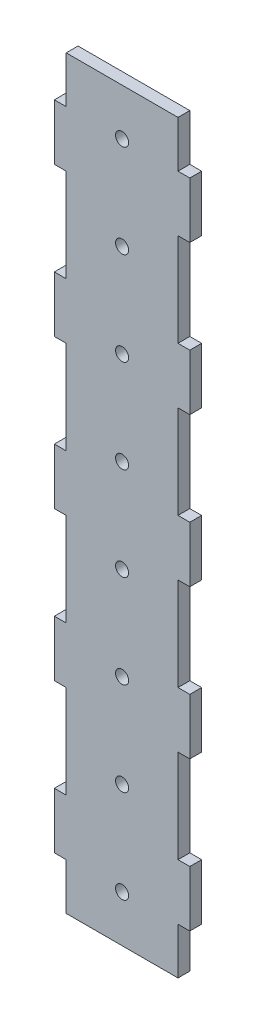
SolidWorks part; units mm, degrees
note: The reader was unsure of these and kept them because the rebuilt part matched: thickness of "Base-Flange1", "Sheet-Metal1", "Sheet-Metal2", "Sheet-Metal3".
ref_plane "Front Plane" through (0, 0, 0) normal (0, 0, 1) x (1, 0, 0)
ref_plane "Top Plane" through (0, 0, 0) normal (0, 1, 0) x (1, 0, 0)
ref_plane "Right Plane" through (0, 0, 0) normal (1, 0, 0) x (0, 0, -1)
sketch "Sketch1" plane through (0, 0, 0) normal (0, 0, 1) x (1, 0, 0)
  line L0 (24.2561, 98.2088) -> (24.2561, 110.7088) construction
  line L1 (6.0811, 110.7088) -> (42.4311, 110.7088)
  line L2 (6.0811, 110.7088) -> (6.0811, -89.2912)
  line L3 (6.0811, -89.2912) -> (42.4311, -89.2912)
  line L4 (42.4311, 110.7088) -> (42.4311, -89.2912)
  line L5 (24.2561, -76.7912) -> (24.2561, -89.2912) construction
  circle A0 centre (24.2561, 98.2088) radius 1.75
  circle A1 centre (24.2561, 73.2088) radius 1.75
  circle A2 centre (24.2561, 48.2088) radius 1.75
  circle A3 centre (24.2561, 23.2088) radius 1.75
  circle A4 centre (24.2561, -1.7912) radius 1.75
  circle A5 centre (24.2561, -26.7912) radius 1.75
  circle A6 centre (24.2561, -51.7912) radius 1.75
  circle A7 centre (24.2561, -76.7912) radius 1.75
  point P21 (24.2561, 110.7088)
  dimension "D1" = 36.35
  dimension "D2" = 200
base flange "Base-Flange1" sketch "Sketch1" thickness 3.175 reverse thickness direction no parameters "D1"=0.7366
sketch "Sketch2" plane through (0, 0, 0) normal (0, 0, 1) x (1, 0, 0)
  line L0 (6.0811, 110.7088) -> (6.0811, -89.2912) construction
  line L1 (6.0811, -101.7912) -> (9.2561, -101.7912)
  line L2 (6.0811, -101.7912) -> (6.0811, -76.7912)
  line L3 (6.0811, -76.7912) -> (9.2561, -76.7912)
  line L4 (9.2561, -101.7912) -> (9.2561, -76.7912)
  line L6 (24.2561, -76.7912) -> (24.2561, -51.7912) construction
  line L7 (39.2561, -101.7912) -> (39.2561, -76.7912)
  line L8 (42.4311, -76.7912) -> (39.2561, -76.7912)
  line L9 (42.4311, -101.7912) -> (42.4311, -76.7912)
  line L10 (42.4311, -101.7912) -> (39.2561, -101.7912)
  line L11 (6.0811, -89.2912) -> (42.4311, -89.2912) construction
  dimension "D1" = 3.175
  dimension "D2" = 25
  dimension "D3" = 12.5
extrude "Cut-Extrude1" cut sketch "Sketch2" against normal blind 10 normal cut yes
pattern_linear "LPattern1" count 6 spacing 40 along (0, 1, 0) of "Cut-Extrude1"
sketch "Bend-Lines1" [suppressed] plane through (0, 0, 0) normal (0, 1, 0) x (1, 0, 0)
sketch "Bounding-Box1" [suppressed] plane through (0, 0, 0) normal (0, 1, 0) x (1, 0, 0)
sheet metal parameters "Sheet-Metal1" thickness 3.175 parameters "D1"=0.7366, "D7"=0.7366
flat pattern "Flat-Pattern1" [suppressed]
sketch "Bend-Lines2" plane through (0, 0, 0) normal (0, 1, 0) x (1, 0, 0)
sketch3d "Bounding-Box2" [suppressed]
  line L0 (44.2561, 110.7088, 0) -> (44.2561, -89.2912, 0) construction
  line L1 (4.2561, 110.7088, 0) -> (4.2561, -89.2912, 0) construction
  line L2 (44.2561, 110.7088, 0) -> (4.2561, 110.7088, 0) construction
  line L3 (44.2561, -89.2912, 0) -> (4.2561, -89.2912, 0) construction
sheet metal parameters "Sheet-Metal2" thickness 3.175 parameters "D1"=0.7366, "D7"=0.7366
flat pattern "Flat-Pattern1"
sketch "Bend-Lines2" plane through (0, 0, 0) normal (0, 1, 0) x (1, 0, 0)
sketch3d "Bounding-Box2" [suppressed]
  line L0 (44.2561, 110.7088, 0) -> (44.2561, -89.2912, 0) construction
  line L1 (4.2561, 110.7088, 0) -> (4.2561, -89.2912, 0) construction
  line L2 (44.2561, 110.7088, 0) -> (4.2561, 110.7088, 0) construction
  line L3 (44.2561, -89.2912, 0) -> (4.2561, -89.2912, 0) construction
sheet metal parameters "Sheet-Metal3" thickness 3.175 parameters "D1"=0.7366, "D7"=0.7366
flat pattern "Flat-Pattern1"
sketch "Bend-Lines2" plane through (0, 0, 0) normal (0, 1, 0) x (1, 0, 0)
sketch3d "Bounding-Box2" [suppressed]
  line L0 (42.4311, 110.7088, 0) -> (42.4311, -89.2912, 0) construction
  line L1 (6.0811, 110.7088, 0) -> (6.0811, -89.2912, 0) construction
  line L2 (42.4311, 110.7088, 0) -> (6.0811, 110.7088, 0) construction
  line L3 (42.4311, -89.2912, 0) -> (6.0811, -89.2912, 0) construction
